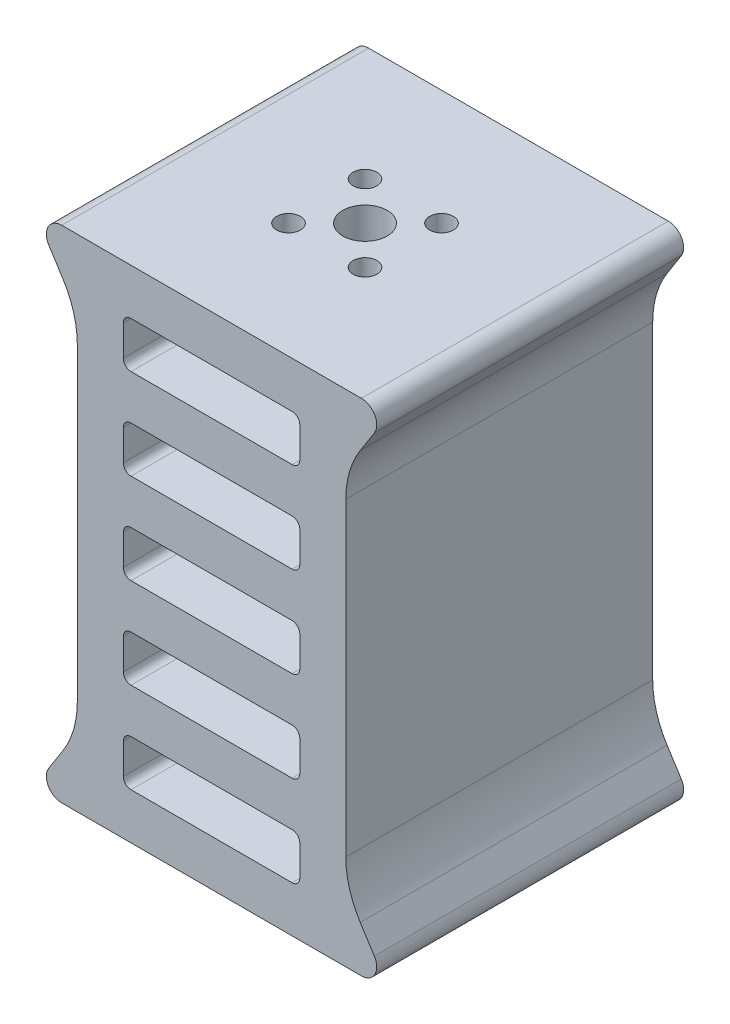
SolidWorks part; units mm, degrees
ref_plane "Front Plane" through (0, 0, 0) normal (0, 0, 1) x (1, 0, 0)
ref_plane "Top Plane" through (0, 0, 0) normal (0, 1, 0) x (1, 0, 0)
ref_plane "Right Plane" through (0, 0, 0) normal (1, 0, 0) x (0, 0, -1)
sketch "Sketch1" plane through (0, 0, 0) normal (0, 0, 1) x (1, 0, 0)
  line L1 (-10.8664, -12.4432) -> (24.1336, -12.4432)
  line L2 (-10.8664, -12.4432) -> (-10.8664, -77.6432)
  line L3 (-10.8664, -77.6432) -> (24.1336, -77.6432)
  line L4 (24.1336, -12.4432) -> (24.1336, -77.6432)
extrude "Boss-Extrude1" add sketch "Sketch1" along normal blind 20 and the other way blind 20
ref_plane "Plane1" through (0, 0, 6) normal (0, 0, 1) x (1, 0, 0)
sketch "Sketch4" plane through (-10.8664, 0, 0) normal (-1, 0, 0) x (0, 0, 1)
  line L0 (20, -12.4432) -> (20, -77.6432) construction
  point P0 (20, -45.0432)
ref_plane "Plane2" through (0, -45.0432, 0) normal (0, 1, 0) x (1, 0, 0)
sketch "Sketch5" plane through (0, 0, 20) normal (0, 0, 1) x (1, 0, 0)
  line L0 (-4.8664, -31.2432) -> (-4.8664, -35.2432)
  line L1 (-3.8664, -30.2432) -> (17.1336, -30.2432)
  line L2 (18.1336, -31.2432) -> (18.1336, -35.2432)
  line L3 (-3.8664, -36.2432) -> (17.1336, -36.2432)
  line L4 (-4.8664, -43.0432) -> (-4.8664, -47.0432)
  line L5 (-3.8664, -18.4432) -> (17.1336, -18.4432)
  line L6 (-4.8664, -19.4432) -> (-4.8664, -23.4432)
  line L7 (-3.8664, -24.4432) -> (17.1336, -24.4432)
  line L16 (18.1336, -19.4432) -> (18.1336, -23.4432)
  line L17 (-3.8664, -42.0432) -> (17.1336, -42.0432)
  line L18 (18.1336, -43.0432) -> (18.1336, -47.0432)
  line L19 (-3.8664, -48.0432) -> (17.1336, -48.0432)
  line L20 (-4.8664, -54.8432) -> (-4.8664, -58.8432)
  line L21 (-3.8664, -53.8432) -> (17.1336, -53.8432)
  line L22 (18.1336, -54.8432) -> (18.1336, -58.8432)
  line L23 (-3.8664, -59.8432) -> (17.1336, -59.8432)
  line L24 (-4.8664, -66.6432) -> (-4.8664, -70.6432)
  line L25 (-3.8664, -65.6432) -> (17.1336, -65.6432)
  line L26 (18.1336, -66.6432) -> (18.1336, -70.6432)
  line L27 (-3.8664, -71.6432) -> (17.1336, -71.6432)
  arc A0 (17.1336, -65.6432) -> (18.1336, -66.6432) centre (17.1336, -66.6432) cw
  arc A1 (18.1336, -70.6432) -> (17.1336, -71.6432) centre (17.1336, -70.6432) cw
  arc A2 (-4.8664, -70.6432) -> (-3.8664, -71.6432) centre (-3.8664, -70.6432) ccw
  arc A3 (-4.8664, -66.6432) -> (-3.8664, -65.6432) centre (-3.8664, -66.6432) cw
  arc A4 (-4.8664, -54.8432) -> (-3.8664, -53.8432) centre (-3.8664, -54.8432) cw
  arc A5 (-4.8664, -58.8432) -> (-3.8664, -59.8432) centre (-3.8664, -58.8432) ccw
  arc A6 (18.1336, -58.8432) -> (17.1336, -59.8432) centre (17.1336, -58.8432) cw
  arc A7 (17.1336, -53.8432) -> (18.1336, -54.8432) centre (17.1336, -54.8432) cw
  arc A8 (17.1336, -42.0432) -> (18.1336, -43.0432) centre (17.1336, -43.0432) cw
  arc A9 (18.1336, -47.0432) -> (17.1336, -48.0432) centre (17.1336, -47.0432) cw
  arc A10 (-4.8664, -47.0432) -> (-3.8664, -48.0432) centre (-3.8664, -47.0432) ccw
  arc A11 (-4.8664, -43.0432) -> (-3.8664, -42.0432) centre (-3.8664, -43.0432) cw
  arc A12 (-4.8664, -31.2432) -> (-3.8664, -30.2432) centre (-3.8664, -31.2432) cw
  arc A13 (-4.8664, -35.2432) -> (-3.8664, -36.2432) centre (-3.8664, -35.2432) ccw
  arc A14 (18.1336, -35.2432) -> (17.1336, -36.2432) centre (17.1336, -35.2432) cw
  arc A15 (17.1336, -30.2432) -> (18.1336, -31.2432) centre (17.1336, -31.2432) cw
  arc A16 (17.1336, -18.4432) -> (18.1336, -19.4432) centre (17.1336, -19.4432) cw
  arc A17 (17.1336, -24.4432) -> (18.1336, -23.4432) centre (17.1336, -23.4432) ccw
  arc A18 (-4.8664, -23.4432) -> (-3.8664, -24.4432) centre (-3.8664, -23.4432) ccw
  arc A19 (-3.8664, -18.4432) -> (-4.8664, -19.4432) centre (-3.8664, -19.4432) ccw
  dimension "D1" = 1
  dimension "D2" = 5
extrude "Cut-Extrude3" cut sketch "Sketch5" against normal up to next
ref_plane "Plane3" through (0, 0, 6) normal (0, 0, 1) x (1, 0, 0)
ref_plane "Plane4" through (0, -45.0432, 0) normal (0, 1, 0) x (1, 0, 0)
sketch "Sketch7" plane through (0, -12.4432, 0) normal (0, 1, 0) x (1, 0, 0)
  circle A0 centre (1.6485, 4.9851) radius 1.55
  circle A1 centre (6.6336, 0) radius 2.9
  circle A2 centre (11.6187, 4.9851) radius 1.55
  circle A3 centre (11.6187, -4.9851) radius 1.55
  circle A4 centre (1.6485, -4.9851) radius 1.55
  point P8 (6.6336, 0)
  dimension "D2" = 3.1
  dimension "D1" = 4
extrude "Cut-Extrude4" cut sketch "Sketch7" against normal blind 10
sketch "Sketch8" plane through (0, 0, 20) normal (0, 0, 1) x (1, 0, 0)
  line L0 (-10.8664, -12.4432) -> (-10.8664, -77.6432) construction
  point P0 (-10.8664, -45.0432)
ref_plane "Plane5" through (0, -45.0432, 0) normal (0, 1, 0) x (1, 0, 0)
mirror "Mirror5" about plane through (0, -45.0432, 0) normal (0, 1, 0) of "Cut-Extrude4"
sketch "Sketch9" plane through (0, 0, -20) normal (0, 0, -1) x (-1, 0, 0)
  line L0 (-24.1336, -12.4432) -> (-26.1656, -12.4432)
  line L1 (-27.8528, -15.5172) -> (-26.0105, -18.4113)
  line L2 (-24.1336, -77.6432) -> (-24.1336, -12.4432) construction
  line L3 (-24.1336, -24.8552) -> (-24.1336, -28.5004)
  line L4 (10.8664, -77.6432) -> (12.8985, -77.6432)
  line L7 (-24.1336, -65.2312) -> (-24.1336, -61.586)
  line L8 (-27.8528, -74.5692) -> (-26.0105, -71.675)
  line L9 (-24.1336, -77.6432) -> (-26.1656, -77.6432)
  line L10 (14.5857, -74.5692) -> (12.7434, -71.675)
  line L11 (10.8664, -65.2312) -> (10.8664, -61.586)
  line L12 (10.8664, -24.8552) -> (10.8664, -28.5004)
  line L13 (14.5857, -15.5172) -> (12.7434, -18.4113)
  line L14 (10.8664, -12.4432) -> (12.8985, -12.4432)
  line L15 (-24.1336, -12.4432) -> (-24.1336, -28.5004)
  line L16 (-24.1336, -61.586) -> (-24.1336, -77.6432)
  line L17 (10.8664, -77.6432) -> (10.8664, -61.586)
  line L18 (10.8664, -28.5004) -> (10.8664, -12.4432)
  arc A0 (-26.1656, -12.4432) -> (-27.8528, -15.5172) centre (-26.1656, -14.4432) ccw
  arc A1 (-26.0105, -18.4113) -> (-24.1336, -24.8552) centre (-36.1336, -24.8552) cw
  arc A2 (-26.0105, -71.675) -> (-24.1336, -65.2312) centre (-36.1336, -65.2312) ccw
  arc A3 (-26.1656, -77.6432) -> (-27.8528, -74.5692) centre (-26.1656, -75.6432) cw
  arc A4 (12.8985, -77.6432) -> (14.5857, -74.5692) centre (12.8985, -75.6432) ccw
  arc A5 (12.7434, -71.675) -> (10.8664, -65.2312) centre (22.8664, -65.2312) cw
  arc A6 (12.7434, -18.4113) -> (10.8664, -24.8552) centre (22.8664, -24.8552) ccw
  arc A7 (12.8985, -12.4432) -> (14.5857, -15.5172) centre (12.8985, -14.4432) cw
  point P17 (-24.1336, -21.3599)
  point P26 (-24.1336, -68.7265)
  point P41 (10.8664, -68.7265)
  point P42 (10.8664, -21.3599)
  line M44 (10.8664, -77.6432) -> (10.8664, -12.4432)
  line M46 (-24.1336, -12.4432) -> (-24.1336, -77.6432)
  dimension "D1" = 2
  dimension "D2" = 12
extrude "Boss-Extrude2" add sketch "Sketch9" against normal up to surface (40 mm away) contours L1 A1 L0 A0 M46 | A3 L9 A2 L8 M46 | L10 A5 L4 A4 M44 | A7 L14 A6 L13 M44 region at (25.6442, -15.9918, -20) region at (25.6442, -74.0945, -20) region at (-12.3771, -74.0945, -20) region at (-12.3771, -15.9918, -20) up to face at (6.6336, -68.6432, 20)
